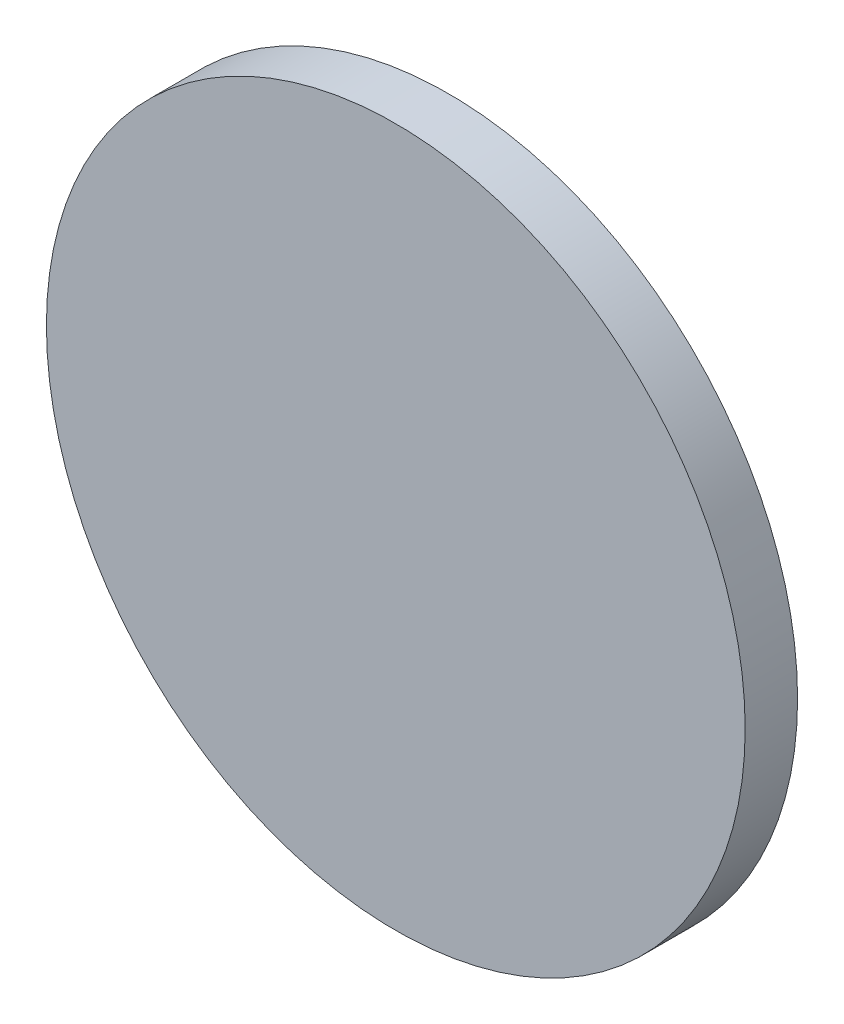
SolidWorks part; units mm, degrees
ref_plane "Plan de face" through (0, 0, 0) normal (0, 0, 1) x (1, 0, 0)
ref_plane "Plan de dessus" through (0, 0, 0) normal (0, 1, 0) x (1, 0, 0)
ref_plane "Plan de droite" through (0, 0, 0) normal (1, 0, 0) x (0, 0, -1)
sketch "Esquisse1" plane through (0, 0, 0) normal (0, 0, 1) x (1, 0, 0)
  circle A0 centre (0, 0) radius 10
  dimension "D1" = 20
extrude "Boss.-Extru.1" add sketch "Esquisse1" along normal blind 1.5
